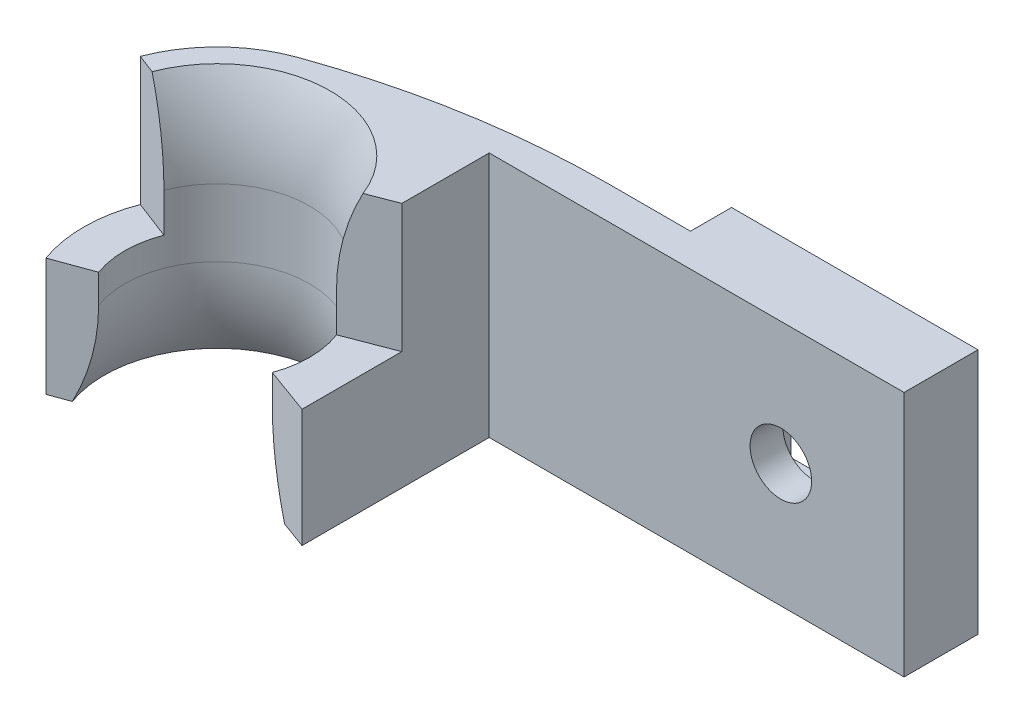
SolidWorks part; units mm, degrees
ref_plane "Front Plane" through (0, 0, 0) normal (0, 0, 1) x (1, 0, 0)
ref_plane "Top Plane" through (0, 0, 0) normal (0, 1, 0) x (1, 0, 0)
ref_plane "Right Plane" through (0, 0, 0) normal (1, 0, 0) x (0, 0, -1)
sketch "Sketch2" plane through (0, 0, 0) normal (0, 1, 0) x (1, 0, 0)
  line L0 (6, 6.75) -> (-14.2, 6.75)
  line L5 (-10, 8.35) -> (6, 8.35)
  line L6 (6, 8.35) -> (6, 6.75)
  line L7 (-14.2, 6.75) -> (-14.2, 0)
  line L8 (-14.2, 0) -> (-16.2, 0)
  line L9 (-25.2, 0) -> (-27.2, 0)
  arc A3 (-16.2, 0) -> (-25.2, 0) centre (-20.7, 0) ccw
  arc A4 (-22.8824, 6.1227) -> (-27.2, 0) centre (-20.7, 0) ccw
  arc A5 (-10, 8.35) -> (-22.8824, 6.1227) centre (-10, -30.0182) ccw
  circle A6 centre (-20.7, 0) radius 6.5 construction
  circle A7 centre (-20.7, 0) radius 4.5 construction
  point P5 (-21.4685, 5.0662)
  dimension "D1" = 6.75
  dimension "D4" = 9
  dimension "D5" = 2
  dimension "D6" = 14.2
  dimension "D3" = 1.6
  dimension "D2" = 6
  dimension "D7" = 16
extrude "Boss-Extrude1" add sketch "Sketch2" along normal mid plane 12
sketch "Sketch3" plane through (0, 0, -6.75) normal (0, 0, 1) x (1, 0, 0)
  circle A0 centre (0, 0) radius 1.5
  dimension "D1" = 3
extrude "Cut-Extrude1" cut sketch "Sketch3" against normal up to next
ref_plane "Plane1" through (0, -0.25, 0) normal (0, 1, 0) x (1, 0, 0)
sketch "Sketch5" plane through (0, -0.25, 0) normal (0, 1, 0) x (1, 0, 0)
  line L0 (-24.9286, -1.5391) -> (-26.808, -2.2231)
  line L1 (-24.9286, -1.5391) -> (-20.7, 0) construction
  line L3 (-27.2, 0) -> (-25.2, 0) construction
  line L5 (-14.2, 0) -> (-14.2, 6.75) construction
  line L6 (-14.2, 0) -> (-14.2, -2.3658)
  line L7 (-20.7, 0) -> (-16.4714, -1.5391) construction
  line L8 (-16.4714, -1.5391) -> (-14.2, -2.3658)
  arc A0 (-16.2, 0) -> (-25.2, 0) centre (-20.7, 0) ccw construction
  arc A1 (-16.4714, -1.5391) -> (-24.9286, -1.5391) centre (-20.7, 0) ccw
  arc A2 (-22.8824, 6.1227) -> (-27.2, 0) centre (-20.7, 0) ccw construction
  arc A3 (-14.2, 0) -> (-26.808, -2.2231) centre (-20.7, 0) ccw
  dimension "D1" = 20
extrude "Boss-Extrude2" add sketch "Sketch5" against normal up to surface (5.75 mm away) up to face at (-13.2165, -6, -4.6733)
sketch "Sketch6" plane through (0, -0.25, 0) normal (0, 1, 0) x (1, 0, 0)
  line L0 (-24.9011, 1.6127) -> (-26.7683, 2.3294)
  line L1 (-24.9011, 1.6127) -> (-20.7, 0) construction
  line L2 (-27.2, 0) -> (-25.2, 0) construction
  line L4 (-14.2, 0) -> (-14.2, 6.75) construction
  line L5 (-14.2, 0) -> (-14.2, 2.4951)
  line L6 (-16.4989, 1.6127) -> (-14.2, 2.4951)
  line L7 (-20.7, 0) -> (-16.4989, 1.6127) construction
  arc A0 (-22.8824, 6.1227) -> (-27.2, 0) centre (-20.7, 0) ccw construction
  arc A1 (-16.2, 0) -> (-25.2, 0) centre (-20.7, 0) ccw construction
  arc A2 (-26.7683, 2.3294) -> (-14.2, 0) centre (-20.7, 0) ccw
  arc A3 (-24.9011, 1.6127) -> (-16.4989, 1.6127) centre (-20.7, 0) ccw
  dimension "D1" = 21
extrude "Cut-Extrude2" cut sketch "Sketch6" along normal up to surface (6.25 mm away) up to face at (-13.2165, 6, -4.6733)
chamfer "Chamfer1" distance 1 angle 45 2 edges at (-20.7, -6, -4.5) (-20.7, 6, -4.5)
fillet "Fillet1" radius 10 2 edges at (-20.7, -5, -4.5) (-20.7, 5, -4.5)
sketch "Sketch7" plane through (0, 0, 0) normal (1, 0, 0) x (0, 0, -1)
  line L0 (8.35, 6) -> (8.35, -6) construction
  line L1 (8.35, 6) -> (10.35, 6)
  line L2 (8.35, 6) -> (8.35, -6)
  line L4 (10.35, 6) -> (10.35, -6)
  line L5 (10.35, -6) -> (8.35, -6)
  point P2 (0, 0)
  point P6 (8.35, -5.885)
  point P9 (8.35, 6)
  dimension "D2" = 2
extrude "Boss-Extrude3" add sketch "Sketch7" along normal mid plane 12
sketch "Sketch8" plane through (0, 0, -10.35) normal (0, 0, -1) x (-1, 0, 0)
  line L1 (-3.1, -3.1) -> (3.1, -3.1)
  line L2 (-3.1, -3.1) -> (-3.1, 3.1)
  line L3 (-3.1, 3.1) -> (3.1, 3.1)
  line L4 (3.1, -3.1) -> (3.1, 3.1)
  line L5 (-3.1, -3.1) -> (3.1, 3.1) construction
  line L6 (-3.1, 3.1) -> (3.1, -3.1) construction
  point P0 (0, 0)
  dimension "D1" = 6.2
extrude "Cut-Extrude3" cut sketch "Sketch8" against normal blind 2
